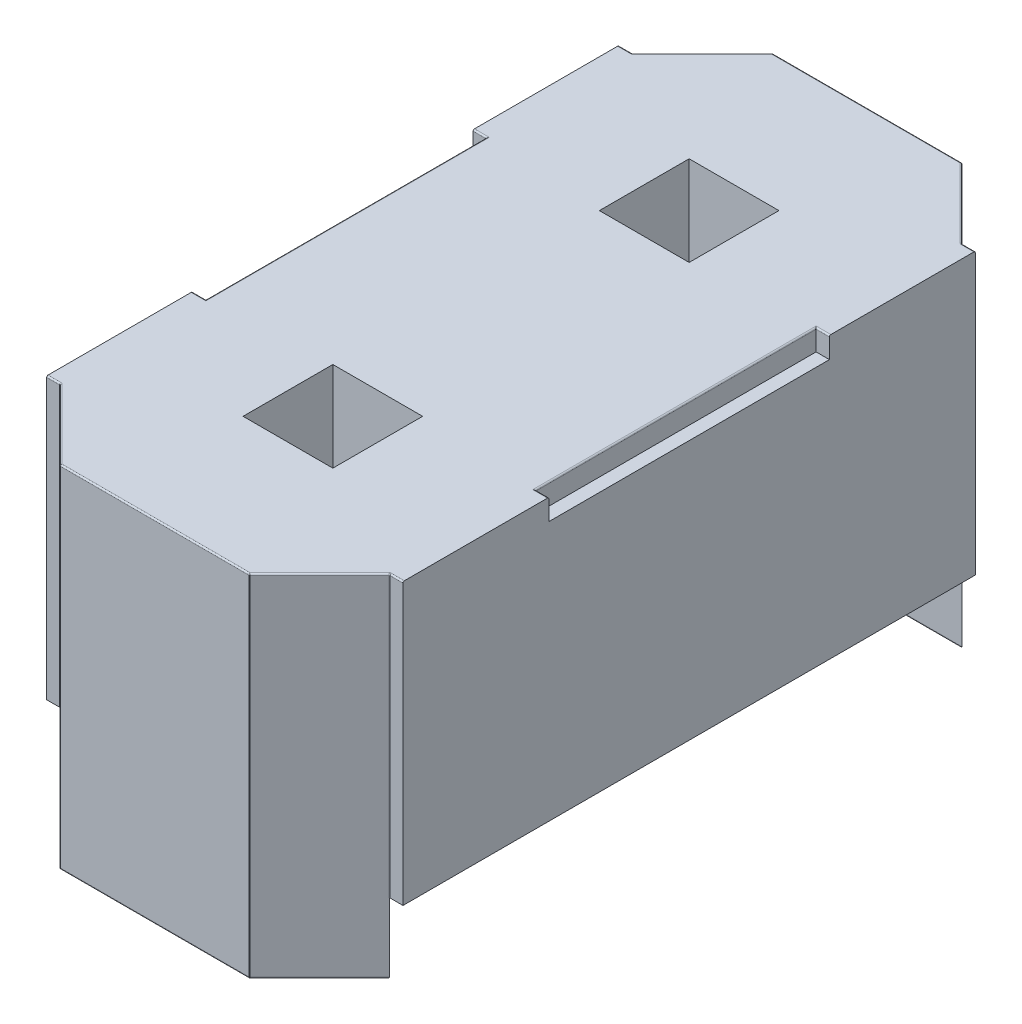
SolidWorks part; units mm, degrees
ref_plane "前视基准面" through (0, 0, 0) normal (0, 0, 1) x (1, 0, 0)
ref_plane "上视基准面" through (0, 0, 0) normal (0, 1, 0) x (1, 0, 0)
ref_plane "右视基准面" through (0, 0, 0) normal (1, 0, 0) x (0, 0, -1)
sketch "Sketch5" plane through (0, 0, 0) normal (0, 1, 0) x (1, 0, 0)
  line L0 (-0.675, 2.54) -> (-1.175, 2.04)
  line L1 (-0.675, 2.54) -> (0.675, 2.54)
  line L2 (-1.175, 2.04) -> (-1.175, -2.04)
  line L3 (-0.675, -2.54) -> (0.675, -2.54)
  line L4 (1.175, 2.04) -> (1.175, -2.04)
  line L7 (0, 2.54) -> (0, -2.54) construction
  line L8 (0.675, 2.54) -> (1.175, 2.04)
  line L9 (-1.175, 0) -> (1.175, 0) construction
  line L10 (0.675, -2.54) -> (1.175, -2.04)
  line L11 (-0.675, -2.54) -> (-1.175, -2.04)
  point P0 (0, 0)
  point P20 (0, 0)
  point P22 (0, -2.54)
  dimension "D1" = 2.35
  dimension "D2" = 5.08
  dimension "D3" = 0.5
  dimension "D4" = 0.5
extrude "Boss-Extrude1" add sketch "Sketch5" along normal blind 2.5
sketch "Sketch7" plane through (0, 2.5, 0) normal (0, 1, 0) x (1, 0, 0)
  line L0 (0, 2.54) -> (0, -2.54) construction
  line L1 (-0.32, 1.59) -> (0.32, 1.59)
  line L2 (-0.32, 1.59) -> (-0.32, 0.95)
  line L3 (-0.32, 0.95) -> (0.32, 0.95)
  line L4 (0.32, 1.59) -> (0.32, 0.95)
  line L5 (-0.32, 1.59) -> (0.32, 0.95) construction
  line L6 (-0.32, 0.95) -> (0.32, 1.59) construction
  line L7 (0.675, 2.54) -> (-0.675, 2.54) construction
  line L8 (-0.675, -2.54) -> (0.675, -2.54) construction
  line L9 (-1.175, 0) -> (1.175, 0) construction
  line L10 (-1.175, 2.04) -> (-1.175, -2.04) construction
  line L11 (1.175, -2.04) -> (1.175, 2.04) construction
  line L12 (-0.32, -0.95) -> (0.32, -0.95)
  line L13 (0.32, -1.59) -> (0.32, -0.95)
  line L14 (-0.32, -1.59) -> (0.32, -1.59)
  line L15 (-0.32, -1.59) -> (-0.32, -0.95)
  line L16 (-0.32, -0.95) -> (0.32, -1.59) construction
  line L17 (-0.32, -1.59) -> (0.32, -0.95) construction
  point P0 (0, 1.27)
  point P17 (0, 0)
  dimension "D1" = 0.64
  dimension "D2" = 0.64
  dimension "D3" = 1.27
extrude "Cut-Extrude1" cut sketch "Sketch7" against normal through all
sketch "Sketch8" plane through (0, 2.5, 0) normal (0, 1, 0) x (1, 0, 0)
  line L0 (0, 2.54) -> (0, -2.54) construction
  line L1 (-1.27, -2.04) -> (-1.175, -2.04)
  line L2 (-1.27, -2.04) -> (-1.27, 2.04)
  line L3 (-1.27, 2.04) -> (-1.175, 2.04)
  line L4 (-1.175, -2.04) -> (-1.175, 2.04)
  line L5 (-1.27, -2.04) -> (-1.175, 2.04) construction
  line L6 (-1.27, 2.04) -> (-1.175, -2.04) construction
  line L7 (-0.675, -2.54) -> (0.675, -2.54) construction
  line L8 (0.675, 2.54) -> (-0.675, 2.54) construction
  line L9 (1.27, 2.04) -> (1.175, -2.04) construction
  line L10 (1.27, -2.04) -> (1.175, 2.04) construction
  line L11 (1.175, -2.04) -> (1.175, 2.04)
  line L12 (1.27, 2.04) -> (1.175, 2.04)
  line L13 (1.27, -2.04) -> (1.27, 2.04)
  line L14 (1.27, -2.04) -> (1.175, -2.04)
  point P0 (-1.2225, 0)
  point P17 (1.2225, 0)
  dimension "D1" = 2.54
extrude "Boss-Extrude2" add sketch "Sketch8" against normal up to surface (2.5 mm away) up to face at (0, 0, -1.27)
sketch "Sketch9" plane through (0, 2.5, 0) normal (0, 1, 0) x (1, 0, 0)
  line L0 (-1.27, 0) -> (1.27, 0) construction
  line L1 (-1.27, 2.04) -> (-1.27, -2.04) construction
  line L2 (1.27, -2.04) -> (1.27, 2.04) construction
  line L3 (0, 2.54) -> (0, -2.54) construction
  line L4 (-1.175, 1) -> (-1.27, 1)
  line L5 (-1.175, 1) -> (-1.175, -1)
  line L6 (-1.175, -1) -> (-1.27, -1)
  line L7 (-1.27, 1) -> (-1.27, -1)
  line L8 (-1.175, 1) -> (-1.27, -1) construction
  line L9 (-1.175, -1) -> (-1.27, 1) construction
  line L10 (0.675, 2.54) -> (-0.675, 2.54) construction
  line L11 (-0.675, -2.54) -> (0.675, -2.54) construction
  line L12 (1.175, -1) -> (1.27, 1) construction
  line L13 (1.175, 1) -> (1.27, -1) construction
  line L14 (1.27, 1) -> (1.27, -1)
  line L15 (1.175, -1) -> (1.27, -1)
  line L16 (1.175, 1) -> (1.175, -1)
  line L17 (1.175, 1) -> (1.27, 1)
  point P6 (-1.2225, 0)
  point P22 (1.2225, 0)
  dimension "D1" = 2
extrude "Cut-Extrude2" cut sketch "Sketch9" against normal blind 0.15
ref_plane "Plane3" through (10, 0, 0) normal (1, 0, 0) x (0, 0, -1)
sketch "Sketch12" plane through (1.27, 0, 0) normal (1, 0, 0) x (0, 0, -1)
  line L0 (0, 2.5) -> (0, 0) construction
  line L2 (1, 2.5) -> (-1, 2.5) construction
  line L7 (1, 2.5) -> (2.04, 2.5) construction
  line L8 (-2.04, 0.5) -> (2.04, 0.5)
  line L9 (-2.04, 0.5) -> (-2.04, 0)
  line L10 (-2.04, 0) -> (2.04, 0)
  line L11 (2.04, 0.5) -> (2.04, 0)
  line L12 (-2.04, 0.5) -> (2.04, 0) construction
  line L13 (-2.04, 0) -> (2.04, 0.5) construction
  line L14 (-2.04, 0) -> (2.04, 0) construction
  line L15 (2.04, 0) -> (2.04, 2.5) construction
  point P5 (0, 0.25)
  dimension "D1" = 2
extrude "Cut-Extrude3" cut sketch "Sketch12" against normal through all both and the other way through all
chamfer "Chamfer1" distance 0.4 angle 45 8 edges at (-0.32, 0.5, -1.27) (0, 0.5, -0.95) (0.32, 0.5, -1.27) (0, 0.5, -1.59) (0, 0.5, 1.59) (0.32, 0.5, 1.27) (0, 0.5, 0.95) (-0.32, 0.5, 1.27)
fillet "Fillet1" radius 0.01 32 edges at (-1.2225, 2.5, -2.04) (-0.925, 2.5, -2.29) (0, 2.5, -2.54) (0.925, 2.5, -2.29) (1.2225, 2.5, -2.04) (1.2225, 2.5, -1) (1.175, 2.5, 0) (1.2225, 2.5, 1) (1.2225, 2.5, 2.04) (0.925, 2.5, 2.29) (0, 2.5, 2.54) (-0.925, 2.5, 2.29) (-1.2225, 2.5, 2.04) (-1.2225, 2.5, 1) (-1.175, 2.5, 0) (-1.2225, 2.5, -1) (0.925, 0, -2.29) (-0.925, 0, -2.29) (0, 0, -2.04) (-0.925, 0, 2.29) (0.925, 0, 2.29) (0, 0, 2.04) (0.675, 1.25, -2.54) (-0.675, 1.25, -2.54) (0, 0, -2.54) (-0.675, 1.25, 2.54) (0.675, 1.25, 2.54) (0, 0, 2.54) (-1.175, 1.5, -2.04) (-1.175, 1.5, 2.04) (1.175, 1.5, -2.04) (1.175, 1.5, 2.04)
